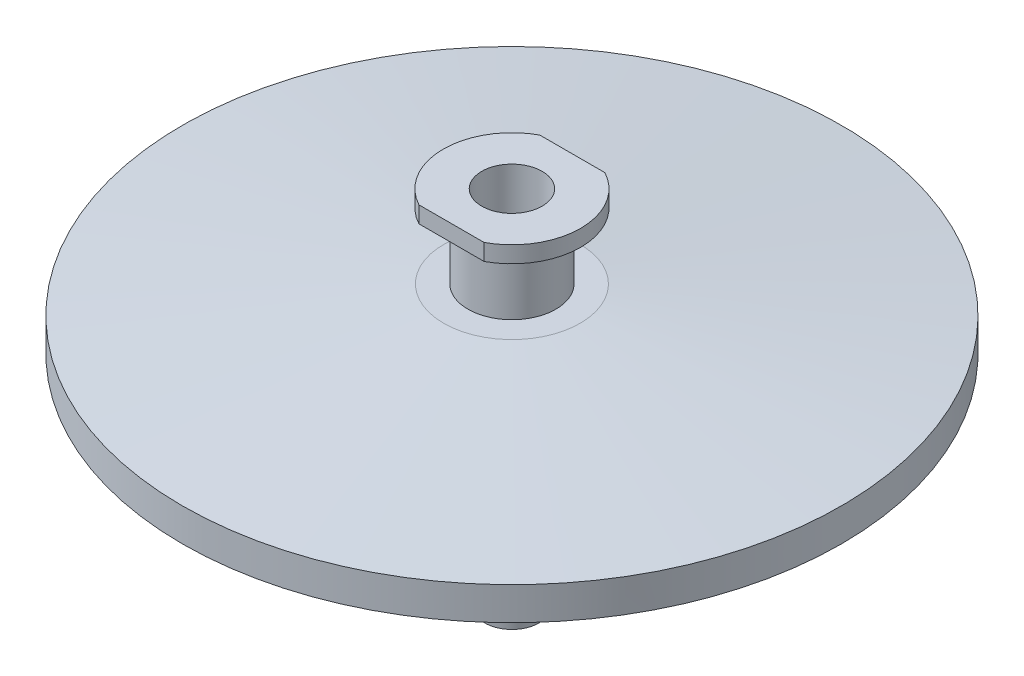
SolidWorks part; units mm, degrees
ref_plane "Front Plane" through (0, 0, 0) normal (0, 0, 1) x (1, 0, 0)
ref_plane "Top Plane" through (0, 0, 0) normal (0, 1, 0) x (1, 0, 0)
ref_plane "Right Plane" through (0, 0, 0) normal (1, 0, 0) x (0, 0, -1)
sketch "Sketch1" plane through (0, 0, 0) normal (0, 1, 0) x (1, 0, 0)
  circle A0 centre (0, 0) radius 15.24
  dimension "D1" = 30.48
extrude "Boss-Extrude1" add sketch "Sketch1" along normal blind 0.762 and the other way blind 0.762
sketch "Sketch2" plane through (0, 0, 0) normal (0, 1, 0) x (1, 0, 0)
  circle A0 centre (0, 0) radius 13.97
  circle A1 centre (0, 0) radius 15.24 construction
  dimension "D1" = 1.27
extrude "Boss-Extrude2" add sketch "Sketch2" along normal blind 0.127 and the other way blind 0.127 separate body
sketch "Sketch3" plane through (0, 0.762, 0) normal (0, 1, 0) x (1, 0, 0)
  circle A1 centre (0, 0) radius 15.24
  circle A2 centre (0, 0) radius 15.24
  dimension "D1" = 0
extrude "Boss-Extrude3" add sketch "Sketch3" along normal blind 1.27 draft 84
sketch "Sketch4" plane through (0, -0.762, 0) normal (0, -1, 0) x (1, 0, 0)
  circle A1 centre (0, 0) radius 15.24
  circle A2 centre (0, 0) radius 15.24
  dimension "D1" = 0
extrude "Boss-Extrude4" add sketch "Sketch4" along normal blind 1.27 draft 84
sketch "Sketch5" plane through (0, 2.032, 0) normal (0, 1, 0) x (1, 0, 0)
  circle A0 centre (0, 0) radius 2.032
  circle A1 centre (0, 0) radius 1.397
  dimension "D1" = 4.064
  dimension "D2" = 0.635
extrude "Boss-Extrude5" add sketch "Sketch5" along normal blind 3.81
sketch "Sketch6" plane through (0, 5.842, 0) normal (0, 1, 0) x (1, 0, 0)
  circle A0 centre (0, 0) radius 3.175
  circle A1 centre (0, 0) radius 2.032
  circle A2 centre (0, 0) radius 2.032
  dimension "D2" = 6.35
  dimension "D1" = 0
extrude "Boss-Extrude6" add sketch "Sketch6" against normal blind 0.762
sketch "Sketch7" plane through (0, 0, 0) normal (1, 0, 0) x (0, 0, -1)
  line L0 (3.175, 5.842) -> (-3.175, 5.842) construction
  line L1 (-3.175, 5.08) -> (-2.794, 5.08)
  line L2 (-3.175, 5.08) -> (-3.175, 5.842)
  line L3 (-3.175, 5.842) -> (-2.794, 5.842)
  line L4 (-2.794, 5.08) -> (-2.794, 5.842)
  line L6 (3.175, 5.08) -> (2.794, 5.08)
  line L7 (3.175, 5.08) -> (3.175, 5.842)
  line L8 (3.175, 5.842) -> (2.794, 5.842)
  line L9 (2.794, 5.08) -> (2.794, 5.842)
  dimension "D1" = 0.381
  dimension "D2" = 0.381
extrude "Cut-Extrude1" cut sketch "Sketch7" against normal through all both and the other way through all
sketch "Sketch8" plane through (0, -2.032, 0) normal (0, -1, 0) x (1, 0, 0)
  circle A0 centre (0, 0) radius 2.032
  circle A1 centre (0, 0) radius 1.397
  dimension "D1" = 4.064
  dimension "D2" = 0.635
extrude "Boss-Extrude7" add sketch "Sketch8" along normal blind 8.89 draft 5 contours A1 | A0 A1 region at (-1.9745, -2.032, 0) region at (0, -2.032, 0)
extrude "Cut-Extrude2" cut sketch "Sketch8<3>" along normal blind 8.89 draft 5 contours A1 region at (0, -2.032, 0)
sketch "Sketch8<3>" plane through (0, -2.032, 0) normal (0, -1, 0) x (1, 0, 0) same geometry as "Sketch8"
ref_plane "Plane1" through (0, -7.112, 0) normal (0, -1, 0) x (-1, 0, 0)
sketch "Sketch9" plane through (0, -7.112, 0) normal (0, -1, 0) x (-1, 0, 0)
  circle A0 centre (0, 0) radius 1.27
  circle A1 centre (0, 0) radius 0.635
  dimension "D1" = 0.635
  dimension "D2" = 1.27
